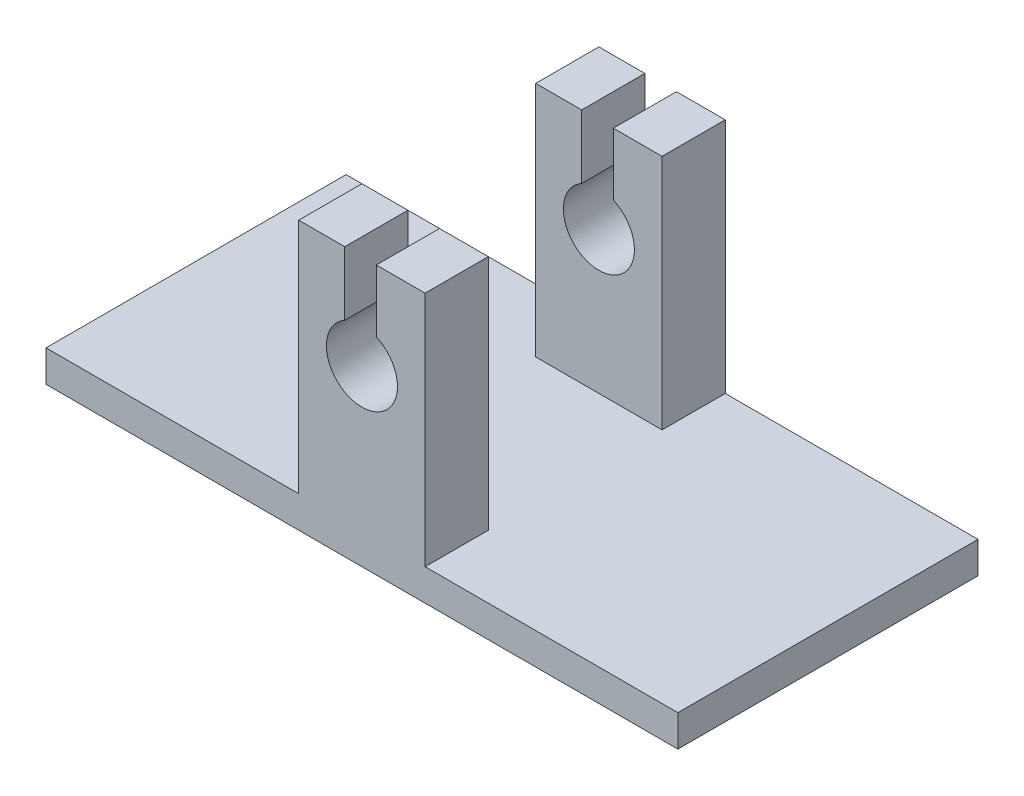
SolidWorks part; units mm, degrees
ref_plane "Front Plane" through (0, 0, 0) normal (0, 0, 1) x (1, 0, 0)
ref_plane "Top Plane" through (0, 0, 0) normal (0, 1, 0) x (1, 0, 0)
ref_plane "Right Plane" through (0, 0, 0) normal (1, 0, 0) x (0, 0, -1)
sketch "Sketch2" plane through (0, 0, 0) normal (0, 1, 0) x (1, 0, 0)
  line L1 (-127, -60.325) -> (127, -60.325)
  line L2 (-127, -60.325) -> (-127, 60.325)
  line L3 (-127, 60.325) -> (127, 60.325)
  line L4 (127, -60.325) -> (127, 60.325)
  line L5 (-127, -60.325) -> (127, 60.325) construction
  line L6 (-127, 60.325) -> (127, -60.325) construction
  point P0 (0, 0)
  dimension "D1" = 120.65
  dimension "D2" = 254
extrude "Boss-Extrude2" add sketch "Sketch2" along normal blind 12.7
sketch "Sketch4" plane through (0, 12.7, 0) normal (0, 1, 0) x (1, 0, 0)
  line L0 (-127, -60.325) -> (0, -60.325) construction
  line L1 (-127, -60.325) -> (127, -60.325) construction
  line L2 (0, -60.325) -> (0, -47.625) construction
  line L3 (0, -47.625) -> (25.4, -47.625) construction
  line L4 (25.4, -47.625) -> (25.4, -34.925) construction
  line L6 (-25.4, -60.325) -> (25.4, -60.325)
  line L7 (-25.4, -60.325) -> (-25.4, -34.925)
  line L8 (-25.4, -34.925) -> (25.4, -34.925)
  line L9 (25.4, -60.325) -> (25.4, -34.925)
  line L10 (-25.4, -60.325) -> (25.4, -34.925) construction
  line L11 (-25.4, -34.925) -> (25.4, -60.325) construction
  dimension "D1" = 12.7
  dimension "D2" = 25.4
  dimension "D3" = 12.7
extrude "Boss-Extrude3" add sketch "Sketch4" along normal blind 95.25
mirror "Mirror1" about plane through (0, 0, 0) normal (0, 0, 1) of "Boss-Extrude3"
sketch "Sketch6" plane through (0, 0, 60.325) normal (0, 0, 1) x (1, 0, 0)
  line L0 (-127, 0) -> (127, 0) construction
  line L1 (-25.4, 107.95) -> (25.4, 107.95) construction
  line L4 (-6.9118, 107.95) -> (5.7882, 107.95)
  line L5 (-6.9118, 107.95) -> (-6.9118, 82.3544)
  line L7 (5.7882, 107.95) -> (5.7882, 82.9125)
  arc A0 (-6.9118, 82.3544) -> (5.7882, 82.9125) centre (0, 69.85) ccw
  point P4 (-6.9118, 107.95)
  dimension "D1" = 28.575
  dimension "D2" = 69.85
  dimension "D3" = 12.7
extrude "Cut-Extrude1" cut sketch "Sketch6" against normal through all
